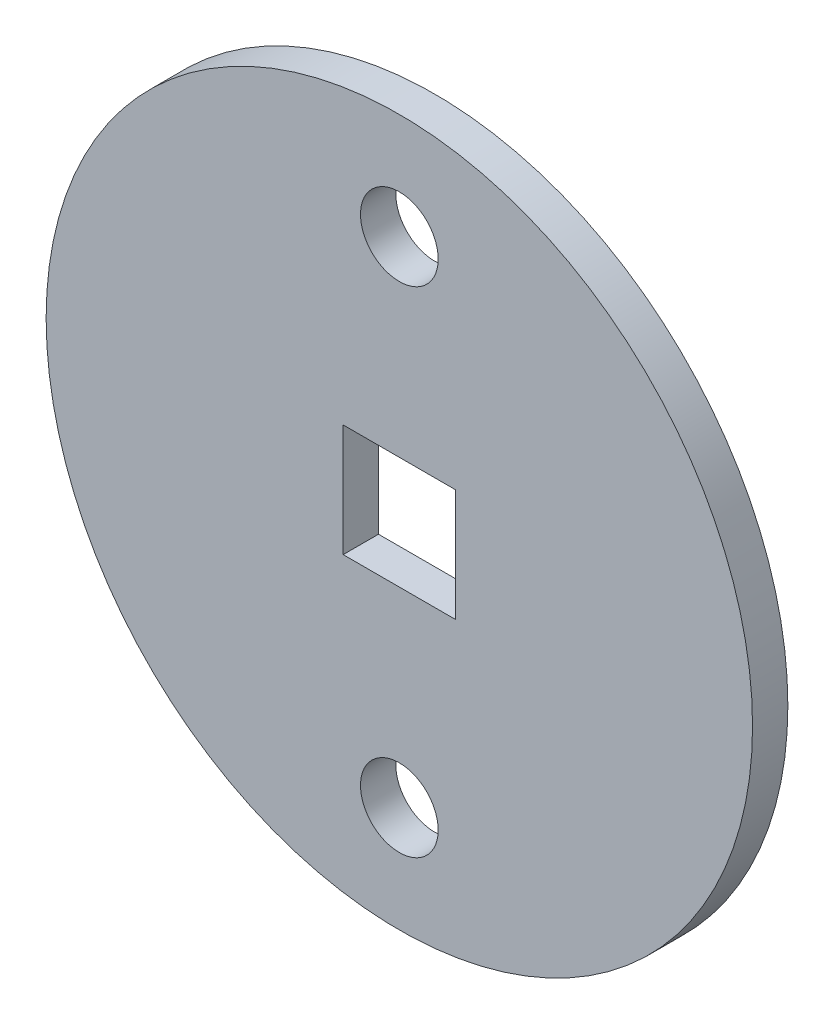
SolidWorks part; units mm, degrees
material "Plain Carbon Steel"
ref_plane "Front Plane" through (0, 0, 0) normal (0, 0, 1) x (1, 0, 0)
ref_plane "Top Plane" through (0, 0, 0) normal (0, 1, 0) x (1, 0, 0)
ref_plane "Right Plane" through (0, 0, 0) normal (1, 0, 0) x (0, 0, -1)
sketch "Sketch1" plane through (0, 0, 0) normal (0, 0, 1) x (1, 0, 0)
  circle A0 centre (0, 0) radius 10
  circle A1 centre (0, 7) radius 1.1
  circle A2 centre (0, -7) radius 1.1
  dimension "D1" = 20
  dimension "D2" = 7
  dimension "D4" = 2.2
  dimension "D5" = 2.2
  dimension "D3" = 7
base flange "Base-Flange1" sketch "Sketch1" thickness 1 reverse thickness direction no parameters "D1"=1.6
sketch "Sketch6" plane through (0, 0, 0) normal (0, 0, 1) x (1, 0, 0)
  line L2 (1.59, 0) -> (1.59, 1.59)
  line L3 (1.59, 0) -> (1.59, -1.59)
  line L4 (1.59, 1.59) -> (-1.59, 1.59)
  line L5 (-1.59, 1.59) -> (-1.59, -1.59)
  line L6 (-1.59, -1.59) -> (1.59, -1.59)
  dimension "D3" = 1.59
  dimension "D4" = 1.59
extrude "Cut-Extrude1" cut sketch "Sketch6" against normal blind 10 normal cut yes
sketch "Bend-Lines1" [suppressed] plane through (0, 0, 0) normal (0, 1, 0) x (1, 0, 0)
sketch "Bounding-Box1" [suppressed] plane through (0, 0, 0) normal (0, 1, 0) x (1, 0, 0)
sheet metal parameters "Sheet-Metal8" thickness 1 parameters "D1"=1.6
flat pattern "Flat-Pattern8" [suppressed]
sketch "Bend-Lines2" plane through (0, 0, 0) normal (0, 1, 0) x (1, 0, 0)
sketch3d "Bounding-Box2" [suppressed]
  line L0 (-9.9657, 10.0341, 0) -> (-10.0341, -9.9656, 0) construction
  line L1 (10.034, 9.9656, 0) -> (9.9656, -10.0341, 0) construction
  line L2 (-9.9657, 10.0341, 0) -> (10.034, 9.9656, 0) construction
  line L3 (-10.0341, -9.9656, 0) -> (9.9656, -10.0341, 0) construction
sheet metal parameters "Sheet-Metal9" thickness 1 parameters "D1"=1.6
flat pattern "Flat-Pattern8"
sketch "Bend-Lines2" plane through (0, 0, 0) normal (0, 1, 0) x (1, 0, 0)
sketch3d "Bounding-Box2" [suppressed]
  line L0 (9.9657, 10.0341, 0) -> (10.0341, -9.9656, 0) construction
  line L1 (-10.034, 9.9656, 0) -> (-9.9656, -10.0341, 0) construction
  line L2 (9.9657, 10.0341, 0) -> (-10.034, 9.9656, 0) construction
  line L3 (10.0341, -9.9656, 0) -> (-9.9656, -10.0341, 0) construction
